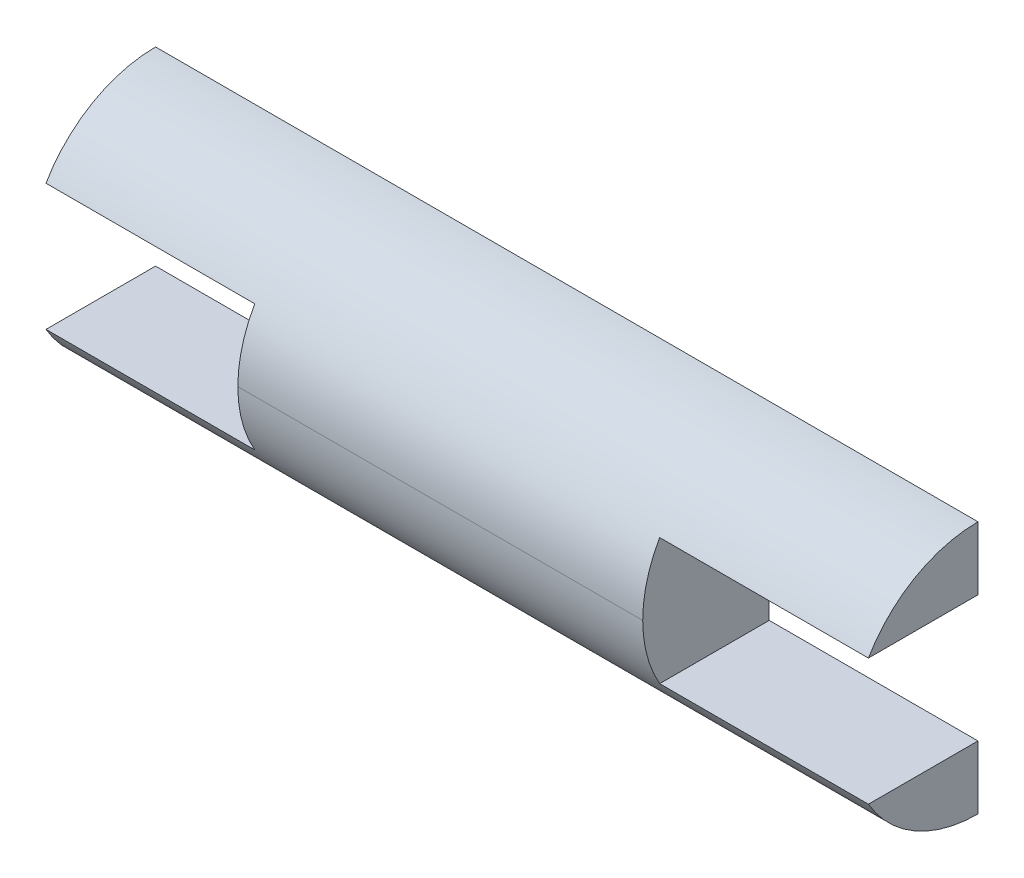
SolidWorks part; units mm, degrees
ref_plane "Front Plane" through (0, 0, 0) normal (0, 0, 1) x (1, 0, 0)
ref_plane "Top Plane" through (0, 0, 0) normal (0, 1, 0) x (1, 0, 0)
ref_plane "Right Plane" through (0, 0, 0) normal (1, 0, 0) x (0, 0, -1)
sketch "Sketch1" plane through (0, 0, 0) normal (0, 0, 1) x (1, 0, 0)
  line L0 (0, 0) -> (13, 0)
  line L1 (13, 0) -> (13, 1)
  line L2 (13, 1) -> (9.7, 1)
  line L3 (9.7, 1) -> (9.7, 3)
  line L4 (9.7, 3) -> (13, 3)
  line L5 (13, 3) -> (13, 4)
  line L6 (13, 4) -> (0, 4)
  line L7 (0, 4) -> (0, 3)
  line L8 (0, 3) -> (3.3, 3)
  line L9 (3.3, 3) -> (3.3, 1)
  line L10 (3.3, 1) -> (0, 1)
  line L11 (0, 1) -> (0, 0)
  dimension "D1" = 13
  dimension "D2" = 1
  dimension "D3" = 1
  dimension "D4" = 1
  dimension "D5" = 1
  dimension "D6" = 4
  dimension "D7" = 3.3
  dimension "D8" = 3.3
extrude "Boss-Extrude1" add sketch "Sketch1" along normal blind 2
fillet "Fillet1" radius 2 2 edges at (6.5, 0, 2) (6.5, 4, 2)
equation "\"slider_length\"=13"
equation "\"D1@Sketch1\"=\"slider_length\""
equation "\"slider_support_thickness\"= 1"
equation "\"D2@Sketch1\"=\"slider_support_thickness\""
equation "\"D5@Sketch1\"=\"slider_support_thickness\""
equation "\"D3@Sketch1\"=\"slider_support_thickness\""
equation "\"D4@Sketch1\"=\"slider_support_thickness\""
equation "\"slider_thickness\"= 4"
equation "\"D6@Sketch1\"=\"slider_thickness\""
equation "\"slider_clamp_width\"= 3.3"
equation "\"D7@Sketch1\"=\"slider_clamp_width\""
equation "\"D8@Sketch1\"=\"slider_clamp_width\""
equation "\"slider_thickness_along_fork\"=2"
equation "\"D1@Boss-Extrude1\"=\"slider_thickness_along_fork\""
equation "\"D1@Fillet1\"=\"slider_thickness\"/2"
